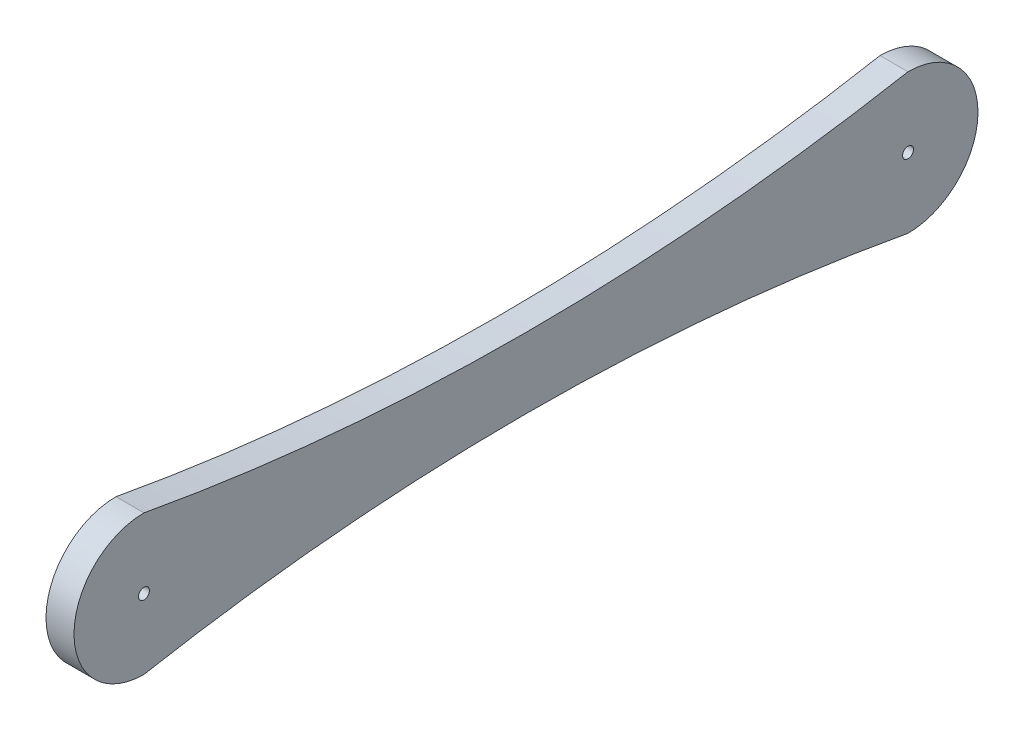
SolidWorks part; units mm, degrees
ref_plane "Front Plane" through (0, 0, 0) normal (0, 0, 1) x (1, 0, 0)
ref_plane "Top Plane" through (0, 0, 0) normal (0, 1, 0) x (1, 0, 0)
ref_plane "Right Plane" through (0, 0, 0) normal (1, 0, 0) x (0, 0, -1)
sketch "Sketch1" plane through (0, 0, 0) normal (1, 0, 0) x (0, 0, -1)
  line L0 (0, -15.9695) -> (0, 0) construction
  line L5 (-198.755, 31.75) -> (198.755, -31.75) construction
  line L6 (-198.755, -31.75) -> (198.755, 31.75) construction
  line L7 (0, 0) -> (0, 15.9695) construction
  circle A0 centre (-173.355, 0) radius 2.4892
  circle A1 centre (173.355, 0) radius 2.4892
  arc A2 (-173.355, 31.75) -> (-173.355, -31.75) centre (-173.355, 0) ccw
  arc A3 (173.355, 31.75) -> (173.355, -31.75) centre (173.355, 0) cw
  arc A4 (-173.355, -31.75) -> (173.355, -31.75) centre (0, -976.0465) cw
  arc A5 (-173.355, 31.75) -> (173.355, 31.75) centre (0, 976.0465) ccw
  point P0 (0, 0)
  point P6 (-198.755, 25.4)
  point P7 (198.755, 25.4)
  point P10 (-173.355, 31.75)
  point P13 (-173.355, -31.75)
  point P14 (173.355, 31.75)
  point P15 (173.355, -31.75)
  point P24 (0, 7.9848)
  point P26 (0, -7.9848)
  dimension "D1" = 397.51
  dimension "D2" = 63.5
extrude "Boss-Extrude1" add sketch "Sketch1" along normal blind 12.7
